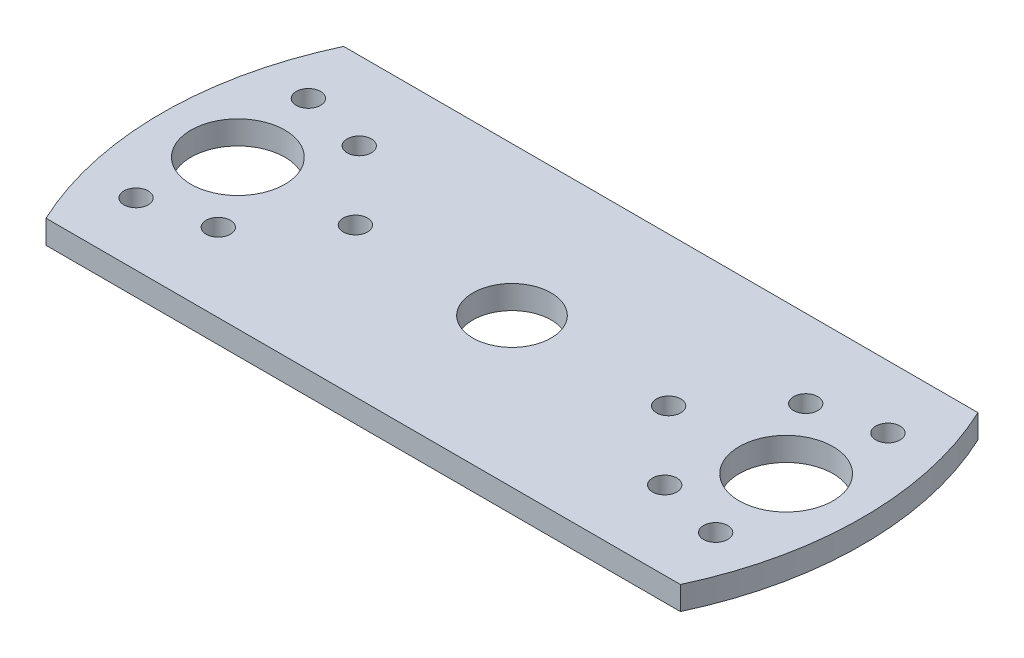
SolidWorks part; units mm, degrees
material "Thornel Mat VMA"
ref_plane "Front Plane" through (0, 0, 0) normal (0, 0, 1) x (1, 0, 0)
ref_plane "Top Plane" through (0, 0, 0) normal (0, 1, 0) x (1, 0, 0)
ref_plane "Right Plane" through (0, 0, 0) normal (1, 0, 0) x (0, 0, -1)
sketch "Sketch1" plane through (0, 0, 0) normal (0, 1, 0) x (1, 0, 0)
  line L0 (0, 0) -> (0, 56.5511) construction
  line L1 (0, 0) -> (118.6796, 0) construction
  line L2 (-62, 19) -> (62, 19)
  line L5 (-62, -19) -> (62, -19)
  line L6 (62, 19) -> (62, 13)
  line L7 (62, 13) -> (59, 13)
  line L8 (59, 13) -> (59, -13)
  line L9 (62, -13) -> (59, -13)
  line L10 (62, -19) -> (62, -13)
  line L11 (-62, -19) -> (-62, -13)
  line L12 (-62, -13) -> (-59, -13)
  line L13 (-59, 13) -> (-59, -13)
  line L14 (-62, 13) -> (-59, 13)
  line L15 (-62, 19) -> (-62, 13)
  circle A0 centre (37, 11) radius 1.55
  circle A1 centre (-37, 11) radius 1.55
  circle A2 centre (-37, -11) radius 1.55
  circle A3 centre (37, -11) radius 1.55
  circle A4 centre (0, 0) radius 5
  circle A5 centre (20, 0) radius 1.55
  circle A6 centre (-20, 0) radius 1.55
  circle A7 centre (35, 0) radius 6
  circle A8 centre (-35, 0) radius 6
  circle A9 centre (28.5, 9) radius 1.55
  circle A10 centre (28.5, -9) radius 1.55
  circle A11 centre (-28.5, -9) radius 1.55
  circle A12 centre (-28.5, 9) radius 1.55
  point P13 (0, 19)
  point P18 (-61, 0)
  point P19 (61, 0)
  point P28 (59, 0)
  dimension "D1" = 3.1
  dimension "D2" = 22
  dimension "D3" = 8
  dimension "D4" = 3.1
  dimension "D5" = 10
  dimension "D6" = 20
  dimension "D11" = 35
  dimension "D12" = 12
  dimension "D13" = 8.5
  dimension "D14" = 2
  dimension "D7" = 38
  dimension "D8" = 124
  dimension "D9" = 3
  dimension "D10" = 6
extrude "Boss-Extrude1" add sketch "Sketch1" along normal blind 3
fillet "Fillet1" radius 3 8 edges at (-62, 1.5, -19) (-62, 1.5, -13) (-62, 1.5, 13) (-62, 1.5, 19) (62, 1.5, 19) (62, 1.5, 13) (62, 1.5, -13) (62, 1.5, -19)
sketch "草图2" plane through (0, 3, 0) normal (0, 1, 0) x (1, 0, 0)
  line L0 (0, 19) -> (0, -19) construction
  line L1 (59, 19) -> (-59, 19) construction
  line L2 (-59, -19) -> (59, -19) construction
  line L3 (0, 0) -> (-21.55, 0) construction
  circle A0 centre (-20, 0) radius 1.55 construction
sketch "草图3" plane through (0, 0, 0) normal (0, -1, 0) x (1, 0, 0)
  circle A0 centre (-30.75, -15) radius 2.1 construction
  circle A1 centre (-30.75, -15) radius 2.1
  circle A2 centre (-30.75, 15) radius 2.1 construction
  circle A3 centre (-30.75, 15) radius 2.1
sketch "草图4" plane through (0, 0, 0) normal (0, -1, 0) x (1, 0, 0)
  line L0 (0, 0) -> (0, 63.4958) construction
  line L1 (-45, 19) -> (-45, -19)
  line L2 (-59, 19) -> (59, 19) construction
  line L3 (59, -19) -> (-59, -19) construction
  line L4 (-45, -19) -> (-67.4332, -19)
  line L5 (-67.4332, -19) -> (-67.4332, 19)
  line L6 (-67.4332, 19) -> (-45, 19)
  line L7 (67.4332, 19) -> (45, 19)
  line L8 (67.4332, -19) -> (67.4332, 19)
  line L9 (45, -19) -> (67.4332, -19)
  line L10 (45, 19) -> (45, -19)
  dimension "D1" = 45
extrude "切除-拉伸1" cut sketch "草图4" against normal blind 10
sketch "草图6" plane through (0, 3, 0) normal (0, 1, 0) x (1, 0, 0)
  line L1 (45, 19) -> (-45, 19) construction
  line L2 (-45, -19) -> (45, -19) construction
  line L3 (-40.5, -19) -> (-45, -19)
  line L4 (-45, -19) -> (-45, 19)
  line L5 (-45, 19) -> (-40.5, 19)
  line L6 (0, 0) -> (0, 31.3174) construction
  line L7 (45, 19) -> (40.5, 19)
  line L8 (45, -19) -> (45, 19)
  line L9 (40.5, -19) -> (45, -19)
  circle A0 centre (0, 0) radius 44.7353 construction
  arc A1 (-40.5, 19) -> (-40.5, -19) centre (0, 0) ccw
  arc A2 (40.5, 19) -> (40.5, -19) centre (0, 0) cw
extrude "切除-拉伸2" cut sketch "草图6" against normal blind 10
